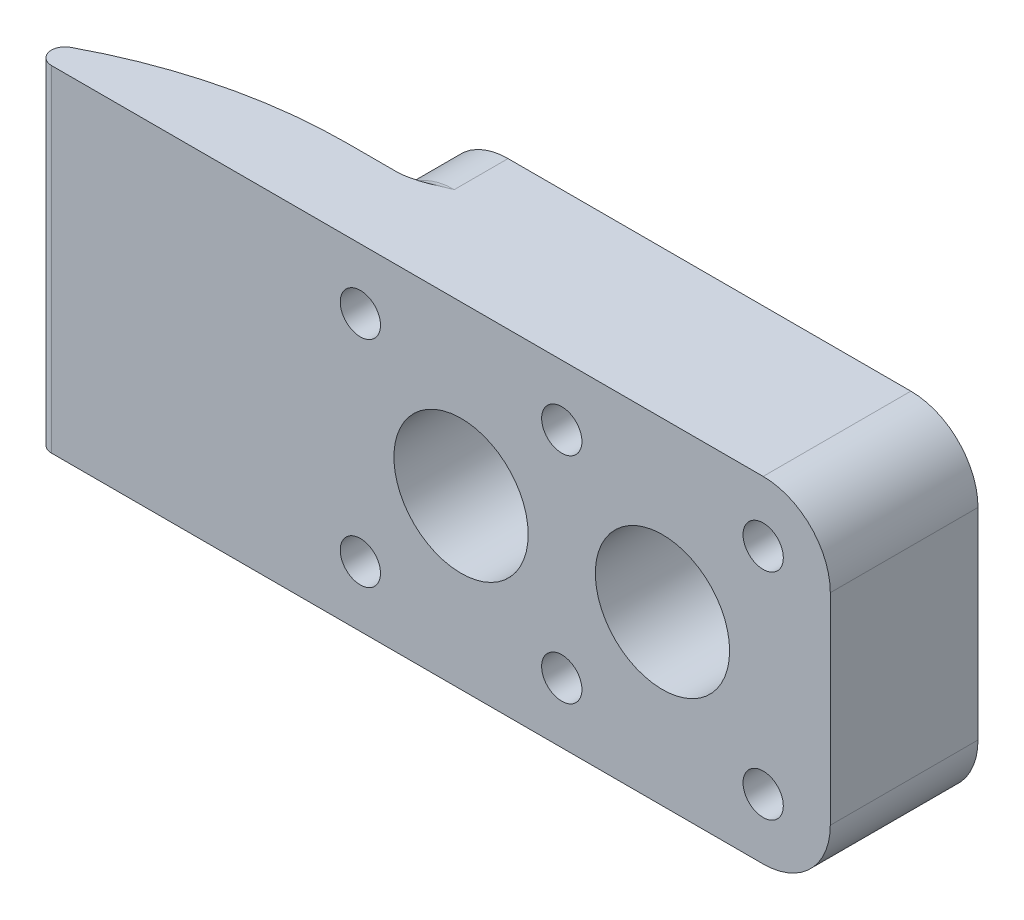
SolidWorks part; units mm, degrees
ref_plane "前视基准面" through (0, 0, 0) normal (0, 0, 1) x (1, 0, 0)
ref_plane "上视基准面" through (0, 0, 0) normal (0, 1, 0) x (1, 0, 0)
ref_plane "右视基准面" through (0, 0, 0) normal (1, 0, 0) x (0, 0, -1)
sketch "草图2" plane through (0, 0, 0) normal (0, 0, 1) x (1, 0, 0)
  line L1 (-20, -12.5) -> (20, -12.5)
  line L2 (-20, -12.5) -> (-20, 12.5)
  line L3 (-20, 12.5) -> (20, 12.5)
  line L4 (20, -12.5) -> (20, 12.5)
  line L5 (-20, -12.5) -> (20, 12.5) construction
  line L6 (-20, 12.5) -> (20, -12.5) construction
  point P0 (0, 0)
  dimension "D1" = 25
  dimension "D2" = 40
extrude "凸台-拉伸1" add sketch "草图2" along normal blind 5
sketch "草图3" plane through (0, 0, 5) normal (0, 0, 1) x (1, 0, 0)
  line L0 (0, 0) -> (50000, 0) construction
  line L1 (0, 0) -> (0, 50000) construction
  circle A0 centre (-15, 8) radius 1.5
  circle A1 centre (0, 8) radius 1.5
  circle A2 centre (15, 8) radius 1.5
  circle A5 centre (15, -8) radius 1.5
  circle A6 centre (0, -8) radius 1.5
  circle A7 centre (-15, -8) radius 1.5
  dimension "D1" = 3
  dimension "3" = 3
  dimension "D2" = 30
  dimension "D3" = 15
  dimension "D4" = 16
extrude "切除-拉伸1" cut sketch "草图3" against normal through all
sketch "草图4" plane through (0, 0, 5) normal (0, 0, 1) x (1, 0, 0)
  line L0 (-15, 8) -> (0, -8) construction
  line L1 (0, 0) -> (0, -50000) construction
  circle A0 centre (-7.5, 0) radius 5
  circle A1 centre (7.5, 0) radius 5
  dimension "D1" = 10
extrude "切除-拉伸2" cut sketch "草图4" against normal through all
sketch "草图6" plane through (0, 0, 0) normal (0, 1, 0) x (1, 0, 0)
  line L0 (-20, -5) -> (-22, -5)
  line L2 (-38, -11) -> (20, -11)
  line L3 (-20, -5) -> (20, -5)
  line L4 (-38.4706, -9.1176) -> (-22, -5) construction
  line L5 (20, -5) -> (20, -11)
  arc A0 (-38.4706, -9.1176) -> (-38, -11) centre (-38, -10) ccw
  arc A1 (-38.4706, -9.1176) -> (-22, -5) centre (-22, -40) cw
  dimension "D2" = 1
  dimension "D1" = 35
  dimension "D3" = 5
  dimension "D4" = 2
extrude "凸台-拉伸2" add sketch "草图6" along normal blind 12.5 and the other way blind 12.5
sketch "草图7" plane through (0, 0, 11) normal (0, 0, 1) x (1, 0, 0)
  circle A0 centre (7.5, 0) radius 5 construction
  circle A1 centre (-15, -8) radius 1.5 construction
  circle A2 centre (-7.5, 0) radius 5 construction
  circle A3 centre (0, -8) radius 1.5 construction
  circle A4 centre (15, -8) radius 1.5 construction
  circle A5 centre (0, 8) radius 1.5 construction
  circle A6 centre (-15, 8) radius 1.5 construction
  circle A7 centre (7.5, 0) radius 5
  circle A8 centre (-15, -8) radius 1.5
  circle A9 centre (-7.5, 0) radius 5
  circle A10 centre (0, -8) radius 1.5
  circle A11 centre (15, -8) radius 1.5
  circle A12 centre (0, 8) radius 1.5
  circle A13 centre (-15, 8) radius 1.5
  circle A14 centre (15, 8) radius 1.5 construction
  circle A15 centre (15, 8) radius 1.5
extrude "切除-拉伸3" cut sketch "草图7" against normal through all
fillet "圆角1" radius 5 4 edges at (20, -12.5, 5.5) (20, 12.5, 5.5) (-20, -12.5, 2.5) (-20, 12.5, 2.5)
sketch "草图9" plane through (0, 0, 0) normal (0, 0, -1) x (-1, 0, 0)
  line L1 (-15, 12.5) -> (-5, 12.5)
  line L2 (-15, 12.5) -> (-15, 17.5)
  line L3 (-15, 17.5) -> (-5, 17.5)
  line L4 (-5, 12.5) -> (-5, 17.5)
  dimension "D1" = 10
  dimension "D2" = 5
extrude "凸台-拉伸3" [suppressed] add sketch "草图9" against normal blind 0.5
ref_plane "基准面1" [suppressed] through (0, 15, 0) normal (0, 1, 0) x (1, 0, 0)
mirror "镜向1" [suppressed] about plane through (0, 15, 0) normal (0, 1, 0)
sketch "草图12" [suppressed] plane through (0, 0, 0) normal (0, 0, -1) x (-1, 0, 0)
  line L1 (-15, 42.5) -> (-5, 42.5)
  line L2 (-15, 42.5) -> (-15, 46.7984)
  line L3 (-15, 46.7984) -> (-5, 46.7984)
  line L4 (-5, 42.5) -> (-5, 46.7984)
  dimension "D1" = 4.2984
  dimension "D2" = 10
extrude "凸台-拉伸4" [suppressed] add sketch "草图12" against normal blind 0.5
sketch "草图11" [suppressed] plane through (0, 0, 0) normal (0, 0, -1) x (-1, 0, 0)
  line L0 (-2, 87.3046) -> (-2, 42.7401) construction
  line L1 (-15, 46.7984) -> (11, 46.7984)
  line L2 (-15, 46.7984) -> (-15, 80.7984)
  line L3 (-15, 80.7984) -> (11, 80.7984)
  line L4 (11, 46.7984) -> (11, 80.7984)
  line L5 (-15, 46.7984) -> (11, 80.7984) construction
  line L6 (-15, 80.7984) -> (11, 46.7984) construction
  line L7 (-25.5535, 63.7984) -> (16.9725, 63.7984) construction
  line L8 (-2, 63.7984) -> (-2, 61.7984) construction
  line L9 (0, 63.7984) -> (0, 61.7984)
  line L10 (-4, 63.7984) -> (-4, 61.7984)
  circle A0 centre (-11, 72.7984) radius 1.5
  circle A1 centre (-11, 54.7984) radius 1.5
  circle A2 centre (7, 54.7984) radius 1.5
  circle A3 centre (7, 72.7984) radius 1.5
  arc A4 (0, 63.7984) -> (-4, 63.7984) centre (-2, 63.7984) ccw
  arc A5 (-4, 61.7984) -> (0, 61.7984) centre (-2, 61.7984) ccw
  point P0 (-2, 63.7984)
  point P19 (-2, 62.7984)
  dimension "D4" = 3
  dimension "D6" = 2
  dimension "D1" = 26
  dimension "D2" = 34
  dimension "D3" = 18
  dimension "D5" = 18
  dimension "D7" = 2
extrude "凸台-拉伸5" [suppressed] add sketch "草图11" against normal blind 3
fillet "圆角2" radius 1 3 edges at (-18.5355, 11.0355, 5) (-18.5355, -11.0355, 5) (-20, 0, 5)
